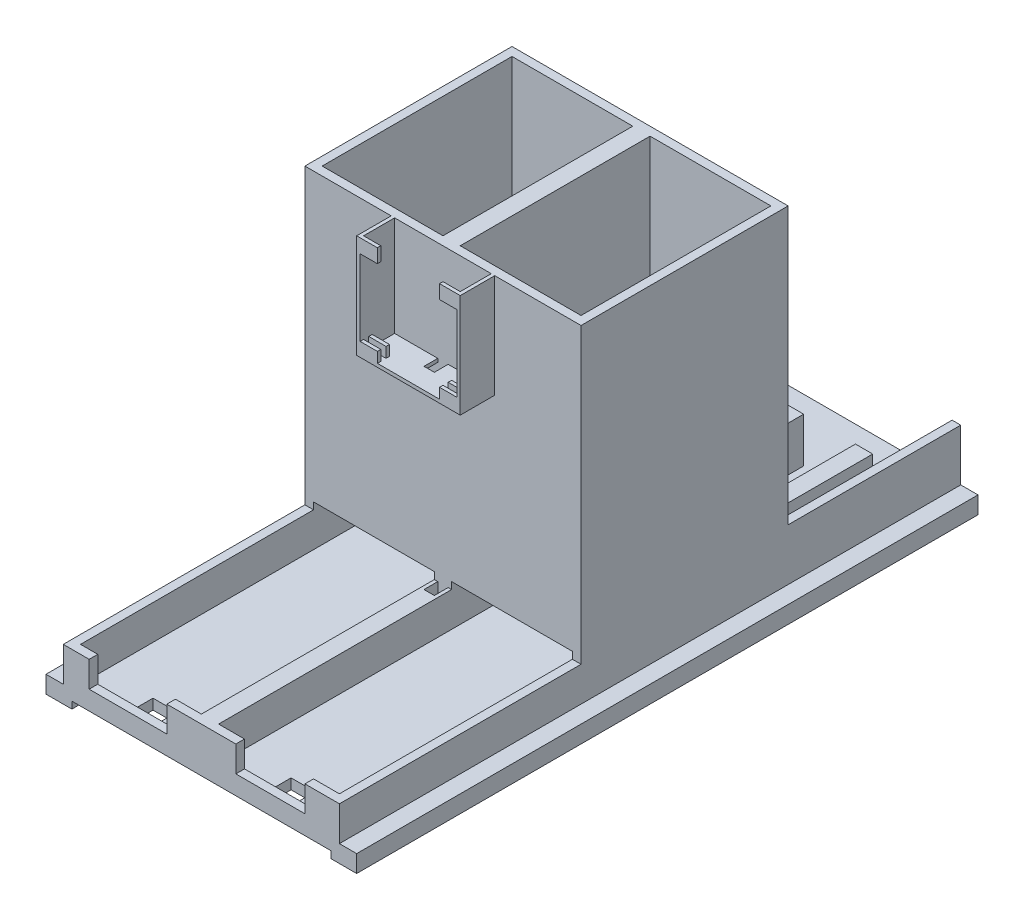
SolidWorks part; units mm, degrees
ref_plane "Front Plane" through (0, 0, 0) normal (0, 0, 1) x (1, 0, 0)
ref_plane "Top Plane" through (0, 0, 0) normal (0, 1, 0) x (1, 0, 0)
ref_plane "Right Plane" through (0, 0, 0) normal (1, 0, 0) x (0, 0, -1)
sketch "Sketch1" plane through (0, 0, 0) normal (0, 1, 0) x (1, 0, 0)
  line L1 (0, 0) -> (80, 0)
  line L2 (0, 0) -> (0, 60)
  line L3 (0, 60) -> (80, 60)
  line L4 (80, 0) -> (80, 60)
sketch "Sketch2" plane through (0, 0, 0) normal (0, 1, 0) x (1, 0, 0)
  line L1 (2.5, 57.5) -> (37.5, 57.5)
  line L2 (2.5, 57.5) -> (2.5, 2.5)
  line L3 (2.5, 2.5) -> (37.5, 2.5)
  line L4 (37.5, 57.5) -> (37.5, 2.5)
  line L5 (42.5, 57.5) -> (77.5, 57.5)
  line L6 (42.5, 57.5) -> (42.5, 2.5)
  line L7 (42.5, 2.5) -> (77.5, 2.5)
  line L8 (77.5, 57.5) -> (77.5, 2.5)
extrude "Boss-Extrude1" add sketch "Sketch1" along normal blind 100
extrude "Cut-Extrude1" cut sketch "Sketch2" along normal blind 95 from offset 5
sketch "Sketch3" plane through (0, 0, 0) normal (0, 0, 1) x (1, 0, 0)
  line L0 (80, 100) -> (80, 0) construction
  line L1 (0, 0) -> (80, 0)
  line L2 (0, 0) -> (0, 5)
  line L3 (0, 5) -> (80, 5)
  line L4 (80, 0) -> (80, 5)
extrude "Boss-Extrude2" add sketch "Sketch3" along normal blind 70
sketch "Sketch4" plane through (0, 5, 0) normal (0, 1, 0) x (1, 0, 0)
  line L0 (80, 0) -> (77.5, 0)
  line L5 (0, 0) -> (0, -70)
  line L18 (0, -70) -> (80, -70)
  line L19 (80, -70) -> (80, 0)
  line L20 (80, 0) -> (0, 0) construction
  line L21 (77.5, 0) -> (77.5, -67.5)
  line L22 (77.5, -67.5) -> (42.5, -67.5)
  line L23 (42.5, -67.5) -> (42.5, 0)
  line L24 (0, 0) -> (80, 0) construction
  line L25 (42.5, 0) -> (37.5, 0)
  line L26 (37.5, 0) -> (37.5, -67.5)
  line L27 (37.5, -67.5) -> (2.5, -67.5)
  line L28 (2.5, -67.5) -> (2.5, 0)
  line L29 (2.5, 0) -> (0, 0)
extrude "Boss-Extrude3" add sketch "Sketch4" along normal blind 10
sketch "Sketch5" plane through (0, 15, 0) normal (0, 1, 0) x (1, 0, 0)
  line L0 (37.5, -67.5) -> (2.5, -67.5) construction
  line L1 (7.5, -67.5) -> (30, -67.5)
  line L2 (7.5, -67.5) -> (7.5, -70)
  line L3 (7.5, -70) -> (30, -70)
  line L4 (30, -67.5) -> (30, -70)
  line L5 (0, -70) -> (80, -70) construction
  line L6 (77.5, -67.5) -> (42.5, -67.5) construction
  line L7 (70, -67.5) -> (50, -67.5)
  line L8 (70, -67.5) -> (70, -70)
  line L9 (70, -70) -> (50, -70)
  line L10 (50, -67.5) -> (50, -70)
  line L11 (0, 0) -> (0, -70) construction
  line L12 (37.5, 0) -> (37.5, -67.5) construction
  line L13 (42.5, -67.5) -> (42.5, 0) construction
  line L14 (77.5, 0) -> (77.5, -67.5) construction
  dimension "D1" = 7.5
  dimension "D2" = 7.5
  dimension "D3" = 7.5
  dimension "D4" = 7.5
extrude "Cut-Extrude2" cut sketch "Sketch5" against normal blind 7.5
sketch "Sketch6" plane through (0, 0, 0) normal (0, 0, 1) x (1, 0, 0)
  line L1 (2.5, 17) -> (37.5, 17)
  line L2 (2.5, 17) -> (2.5, 5)
  line L3 (2.5, 5) -> (37.5, 5)
  line L4 (37.5, 17) -> (37.5, 5)
  line L5 (42.5, 5) -> (77.5, 5)
  line L6 (42.5, 5) -> (42.5, 17)
  line L7 (42.5, 17) -> (77.5, 17)
  line L8 (77.5, 5) -> (77.5, 17)
extrude "Cut-Extrude4" cut sketch "Sketch6" against normal blind 57.5
sketch "Sketch7" plane through (0, 0, -60) normal (0, 0, -1) x (-1, 0, 0)
  circle A0 centre (-20, 11.5) radius 4
  circle A1 centre (-60, 11.5) radius 4
extrude "Cut-Extrude6" cut sketch "Sketch7" against normal up to next
sketch "Sketch9" plane through (0, 0, 0) normal (0, 1, 0) x (1, 0, 0)
  line L1 (0, 60) -> (80, 60)
  line L2 (0, 60) -> (0, 110)
  line L3 (0, 110) -> (80, 110)
  line L4 (80, 60) -> (80, 110)
extrude "Boss-Extrude4" add sketch "Sketch9" along normal blind 5
sketch "Sketch11" plane through (0, 0, 0) normal (0, -1, 0) x (1, 0, 0)
  line L1 (2.5, 70) -> (77.5, 70)
  line L2 (2.5, 70) -> (2.5, 37.5)
  line L3 (2.5, 37.5) -> (77.5, 37.5)
  line L4 (77.5, 70) -> (77.5, 37.5)
  line L6 (0, 70) -> (80, 70) construction
extrude "Cut-Extrude7" cut sketch "Sketch11" against normal blind 2
sketch "Sketch13" plane through (0, 5, 0) normal (0, 1, 0) x (1, 0, 0)
  line L0 (37.5, -67.5) -> (2.5, -67.5) construction
  line L1 (16.5, -67.5) -> (23.5, -67.5)
  line L2 (16.5, -67.5) -> (16.5, -60.5)
  line L3 (16.5, -60.5) -> (23.5, -60.5)
  line L4 (23.5, -67.5) -> (23.5, -60.5)
  line L10 (2.5, 57.5) -> (2.5, -67.5) construction
  line L11 (37.5, -67.5) -> (37.5, 57.5) construction
  line L12 (40, -70) -> (40, -52.9537) construction
  line L13 (30, -70) -> (50, -70) construction
  line L15 (56.5, -67.5) -> (56.5, -60.5)
  line L16 (63.5, -60.5) -> (56.5, -60.5)
  line L17 (63.5, -67.5) -> (63.5, -60.5)
  line L18 (63.5, -67.5) -> (56.5, -67.5)
  point P12 (16.5, -64)
  dimension "D1" = 14
  dimension "D2" = 14
extrude "Cut-Extrude8" cut sketch "Sketch13" against normal through all
sketch "Sketch14" plane through (0, 0, 0) normal (0, 0, 1) x (1, 0, 0)
  line L0 (0, 100) -> (80, 100) construction
  line L1 (25, 100) -> (26, 100)
  line L2 (25, 100) -> (25, 70)
  line L3 (25, 70) -> (26, 70)
  line L4 (26, 100) -> (26, 71)
  line L6 (54, 100) -> (55, 100)
  line L7 (54, 100) -> (54, 71)
  line L8 (54, 70) -> (55, 70)
  line L9 (55, 100) -> (55, 70)
  line L10 (26, 70) -> (54, 70)
  line L12 (26, 71) -> (54, 71)
  dimension "D1" = 30
  dimension "D2" = 1
  dimension "D3" = 1
extrude "Boss-Extrude5" add sketch "Sketch14" along normal blind 10
sketch "Sketch15" plane through (0, 0, 10) normal (0, 0, 1) x (1, 0, 0)
  line L0 (26, 71) -> (26, 100) construction
  line L1 (25, 70) -> (31, 70)
  line L2 (25, 70) -> (25, 74)
  line L3 (25, 74) -> (31, 74)
  line L4 (31, 70) -> (31, 74)
  line L5 (54, 71) -> (26, 71) construction
  line L6 (40, 70) -> (40, 81.9127) construction
  line L7 (25, 70) -> (55, 70) construction
  line L8 (26, 71) -> (26, 100) construction
  line L10 (49, 70) -> (49, 74)
  line L11 (55, 74) -> (49, 74)
  line L12 (55, 70) -> (55, 74)
  line L13 (55, 70) -> (49, 70)
  dimension "D1" = 5
  dimension "D2" = 3
  dimension "D3" = 14
sketch "Sketch17" plane through (0, 0, 10) normal (0, 0, 1) x (1, 0, 0)
  line L1 (25, 100) -> (31, 100)
  line L2 (25, 100) -> (25, 96)
  line L3 (25, 96) -> (31, 96)
  line L4 (31, 100) -> (31, 96)
  line L5 (55, 100) -> (49, 100)
  line L6 (55, 100) -> (55, 96)
  line L7 (55, 96) -> (49, 96)
  line L8 (49, 100) -> (49, 96)
  dimension "D1" = 6
  dimension "D2" = 4
  dimension "D3" = 6
  dimension "D4" = 4
extrude "Boss-Extrude6" add sketch "Sketch15" against normal blind 1
extrude "Boss-Extrude7" add sketch "Sketch15<2>" against normal blind 1 from offset 2.5 offset against normal yes
sketch "Sketch15<2>" plane through (0, 0, 10) normal (0, 0, 1) x (1, 0, 0) same geometry as "Sketch15"
extrude "Boss-Extrude8" add sketch "Sketch17" against normal blind 1
sketch "Sketch18" plane through (0, 71, 0) normal (0, 1, 0) x (1, 0, 0)
  line L5 (42.5, 57.5) -> (42.5, -67.5) construction
  line L7 (54, 0) -> (26, 0) construction
  line L8 (38.5, 0) -> (41.5, 0)
  line L9 (38.5, 0) -> (38.5, -4)
  line L10 (38.5, -4) -> (41.5, -4)
  line L11 (41.5, 0) -> (41.5, -4)
  line L12 (37.5, -67.5) -> (37.5, 57.5) construction
  dimension "D1" = 1
  dimension "D2" = 1
  dimension "D3" = 4
extrude "Cut-Extrude9 (OLED Cable)" cut sketch "Sketch18" against normal through all
sketch "Sketch20" plane through (0, 5, 0) normal (0, 1, 0) x (1, 0, 0)
  line L0 (0, 60) -> (80, 60) construction
  line L1 (62.5, 60) -> (57.5, 60)
  line L2 (62.5, 60) -> (62.5, 65)
  line L3 (62.5, 65) -> (57.5, 65)
  line L4 (57.5, 60) -> (57.5, 65)
  line L5 (80, 60) -> (80, 110) construction
  line L7 (40, 110) -> (40, 60) construction
  line L8 (80, 110) -> (0, 110) construction
  line L9 (17.5, 65) -> (22.5, 65)
  line L10 (22.5, 60) -> (22.5, 65)
  line L11 (17.5, 60) -> (22.5, 60)
  line L12 (17.5, 60) -> (17.5, 65)
  point P8 (60, 60)
  dimension "D1" = 5
  dimension "D2" = 17.5
  dimension "D3" = 5
  dimension "D4" = 40
extrude "Cut-Extrude10 (Solenoid Wire)" cut sketch "Sketch20" against normal through all
sketch "Sketch21" plane through (0, 5, 0) normal (0, 1, 0) x (1, 0, 0)
  line L0 (62.5, 60) -> (80, 60) construction
  line L1 (67.5, 60) -> (72.5, 60)
  line L2 (67.5, 60) -> (67.5, 92)
  line L3 (67.5, 92) -> (72.5, 92)
  line L4 (72.5, 60) -> (72.5, 92)
  line L7 (80, 110) -> (0, 110) construction
  line L9 (40, 60) -> (40, 110) construction
  line L10 (22.5, 60) -> (57.5, 60) construction
  line L11 (0, 110) -> (0, 60) construction
  line L12 (60, 110) -> (60, 60) construction
  line L13 (80, 60) -> (80, 110) construction
  line L15 (47.5, 60) -> (47.5, 92)
  line L16 (52.5, 92) -> (47.5, 92)
  line L17 (52.5, 60) -> (52.5, 92)
  line L18 (52.5, 60) -> (47.5, 60)
  line L19 (27.5, 60) -> (32.5, 60)
  line L20 (27.5, 60) -> (27.5, 92)
  line L21 (32.5, 60) -> (32.5, 92)
  line L22 (27.5, 92) -> (32.5, 92)
  line L23 (7.5, 60) -> (7.5, 92)
  line L24 (12.5, 92) -> (7.5, 92)
  line L25 (12.5, 60) -> (12.5, 92)
  line L26 (12.5, 60) -> (7.5, 60)
  dimension "D1" = 5
  dimension "D2" = 40
  dimension "D3" = 20
  dimension "D4" = 7.5
  dimension "D5" = 32
extrude "Boss-Extrude9 (Solenoid Side Support)" add sketch "Sketch21" along normal blind 13
sketch "Sketch27" plane through (0, 5, 0) normal (0, 1, 0) x (1, 0, 0)
  line L0 (80, 110) -> (0, 110) construction
  line L1 (80, 60) -> (77.5, 60)
  line L2 (80, 60) -> (80, 110)
  line L3 (80, 110) -> (77.5, 110)
  line L4 (77.5, 60) -> (77.5, 110)
  line L6 (0, 60) -> (2.5, 60)
  line L7 (0, 60) -> (0, 110)
  line L8 (0, 110) -> (2.5, 110)
  line L9 (2.5, 60) -> (2.5, 110)
  dimension "D1" = 2.5
  dimension "D2" = 2.5
extrude "Boss-Extrude13 (Solenoid Section Walls)" add sketch "Sketch27" along normal blind 15
sketch "Sketch29" plane through (80, 0, 0) normal (1, 0, 0) x (0, 0, -1)
  line L0 (-70, 0) -> (-70, 15) construction
  line L1 (-70, 5) -> (110, 5)
  line L2 (-70, 5) -> (-70, 0)
  line L3 (-70, 0) -> (110, 0)
  line L4 (110, 5) -> (110, 0)
  line L5 (110, 20) -> (110, 0) construction
  line L6 (-70, 0) -> (110, 0) construction
  dimension "D1" = 5
extrude "Boss-Extrude9 (Guide)" add sketch "Sketch29" along normal blind 5
extrude "Boss-Extrude10 (Guide)" add sketch "Sketch29<3>" against normal blind 5 from offset 80 offset against normal yes
sketch "Sketch29<3>" plane through (80, 0, 0) normal (1, 0, 0) x (0, 0, -1) same geometry as "Sketch29"
